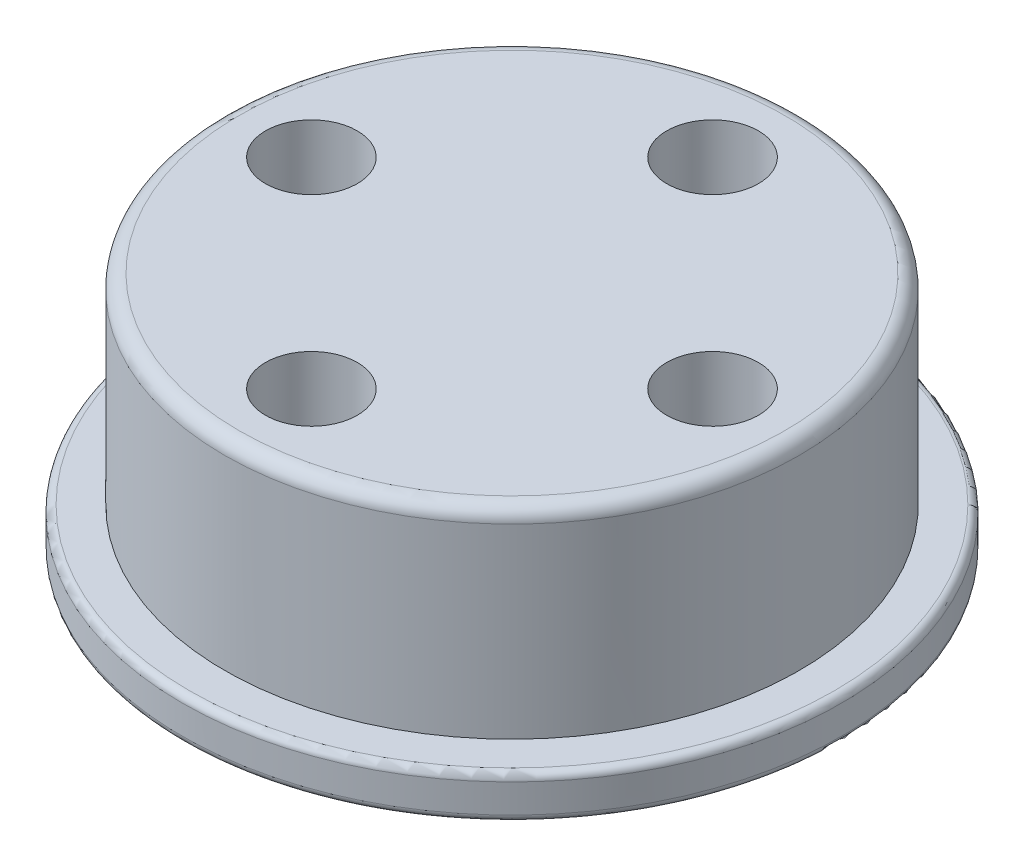
SolidWorks part; units mm, degrees
ref_plane "Front Plane" through (0, 0, 0) normal (0, 0, 1) x (1, 0, 0)
ref_plane "Top Plane" through (0, 0, 0) normal (0, 1, 0) x (1, 0, 0)
ref_plane "Right Plane" through (0, 0, 0) normal (1, 0, 0) x (0, 0, -1)
sketch "Sketch1" plane through (0, 0, 0) normal (0, 0, 1) x (1, 0, 0)
  line L0 (0, 0) -> (0, 8.5) construction
  line L1 (0, 8.5) -> (10.025, 8.5)
  line L2 (10.025, 8.5) -> (10.025, 1.5)
  line L3 (10.025, 1.5) -> (11.5, 1.5)
  line L4 (11.5, 1.5) -> (11.5, 0)
  line L5 (0, 0) -> (0, 8.5)
  line L7 (11.5, 0) -> (0, 0)
  dimension "D1" = 20.05
  dimension "D2" = 23
  dimension "D3" = 1.5
  dimension "D4" = 7
revolve "Revolve1" add sketch "Sketch1" angle 360 about L0
sketch "Sketch2" plane through (0, 0, 0) normal (0, -1, 0) x (1, 0, 0)
  line L0 (0, 0) -> (0, 7) construction
  circle A0 centre (0, 7) radius 1.6
  circle A1 centre (7, 0) radius 1.6
  circle A2 centre (0, -7) radius 1.6
  circle A3 centre (-7, 0) radius 1.6
  point P13 (0, 0)
  dimension "D2" = 3.2
  dimension "D1" = 7
  dimension "D3" = 4
extrude "Cut-Extrude1" cut sketch "Sketch2" against normal through all
hole_wizard "CSK for M3 Flat Head Machine Screw1" positions "3DSketch1" profile "Sketch3" countersink size "M3" standard "ANSI Metric" end condition through all
sketch3d "3DSketch1"
  line L0 (0, 8.5, 7) -> (0, 0, 7) construction
  line L1 (7, 8.5, 0) -> (7, 0, 0) construction
  line L2 (0, 8.5, -7) -> (0, 0, -7) construction
  line L3 (-7, 8.5, 0) -> (-7, 0, 0) construction
  point P0 (0, 0, 7)
  point P4 (7, 0, 0)
  point P8 (0, 0, -7)
  point P12 (-7, 0, 0)
sketch "Sketch3" plane through (0, 0, 7) normal (1, 0, 0) x (0, 0, -1)
  line L0 (0, 0) -> (0, 8.5)
  line L1 (0, 8.5) -> (1.4, 8.5)
  line L2 (1.4, 8.5) -> (1.4, 1.85)
  line L3 (1.4, 1.85) -> (3.25, 0)
  line L5 (3.25, 0) -> (0, 0)
  line L6 (-1.4, 1.85) -> (-3.25, 0) construction
  line L11 (0, -6.35) -> (0, 107.95) construction
  dimension "Thru Hole Dia." = 2.8
  dimension "Thru Hole Depth" = 8.5
  dimension "Near C'Sink Dia." = 6.5
  dimension "Near C'Sink Angle" = 90
fillet "Fillet1" radius 0.5 1 edges at (0, 8.5, -10.025)
fillet "Fillet2" radius 0.25 2 edges at (0, 0, -11.5) (0, 1.5, -11.5)
